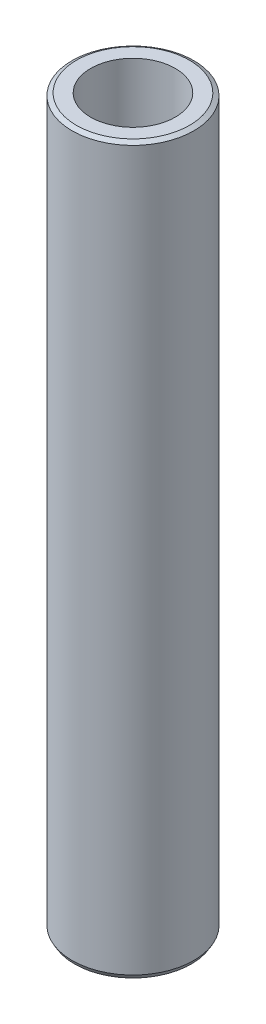
SolidWorks part; units mm, degrees
ref_plane "Front Plane" through (0, 0, 0) normal (0, 0, 1) x (1, 0, 0)
ref_plane "Top Plane" through (0, 0, 0) normal (0, 1, 0) x (1, 0, 0)
ref_plane "Right Plane" through (0, 0, 0) normal (1, 0, 0) x (0, 0, -1)
sketch "Sketch1" plane through (0, 0, 0) normal (0, 1, 0) x (1, 0, 0)
  circle A0 centre (0, 0) radius 42.5
  dimension "SHAFT_OD" = 85
extrude "Boss-Extrude1" add sketch "Sketch1" along normal blind 506.4586
sketch "Sketch2" plane through (0, 0, 0) normal (0, 1, 0) x (1, 0, 0)
  circle A0 centre (0, 0) radius 29.5403
  dimension "BORE_D" = 59.0806
extrude "Cut-Extrude1" cut sketch "Sketch2" along normal through all
chamfer "Chamfer1" distance 1.7563 angle 60 2 edges at (0, 506.4586, 42.5) (0, 0, 42.5) first distance on face at (0, 506.4586, 42.5) first distance on face at (0, 0, 29.5403)
